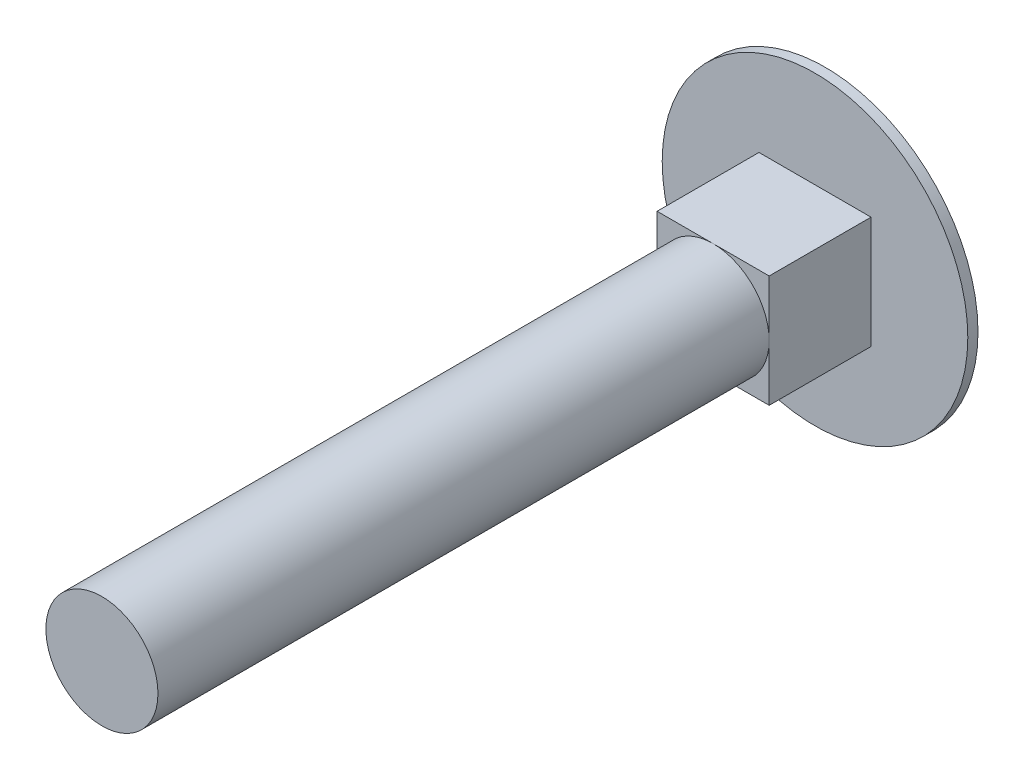
SolidWorks part; units mm, degrees
ref_plane "Plan de face" through (0, 0, 0) normal (0, 0, 1) x (1, 0, 0)
ref_plane "Plan de dessus" through (0, 0, 0) normal (0, 1, 0) x (1, 0, 0)
ref_plane "Plan de droite" through (0, 0, 0) normal (1, 0, 0) x (0, 0, -1)
sketch "Esquisse1" plane through (0, 0, 0) normal (0, 0, 1) x (1, 0, 0)
  circle A0 centre (0, 0) radius 2.75
  dimension "D1" = 5.5
extrude "Boss.-Extru.1" add sketch "Esquisse1" along normal blind 30
sketch "Esquisse2" plane through (0, 0, 0) normal (0, 0, -1) x (-1, 0, 0)
  line L1 (2.75, 2.75) -> (-2.75, 2.75)
  line L2 (2.75, 2.75) -> (2.75, -2.75)
  line L3 (2.75, -2.75) -> (-2.75, -2.75)
  line L4 (-2.75, 2.75) -> (-2.75, -2.75)
  line L5 (2.75, 2.75) -> (-2.75, -2.75) construction
  line L6 (2.75, -2.75) -> (-2.75, 2.75) construction
  point P0 (0, 0)
  dimension "D1" = 5.5
  dimension "D2" = 5.5
extrude "Boss.-Extru.2" add sketch "Esquisse2" along normal blind 5 contours L2 L3 L4 L1
sketch "Esquisse3" plane through (0, 0, -5) normal (0, 0, -1) x (-1, 0, 0)
  circle A0 centre (0, 0) radius 7.5
  dimension "D1" = 15
extrude "Boss.-Extru.3" add sketch "Esquisse3" along normal blind 0.5 contours A0
dome "Dôme1" faces to dome 1 distance 2.5 reverse direction no elliptical dome no face at (-7.5, 0, -5.5) parameters "D1"=2.5
